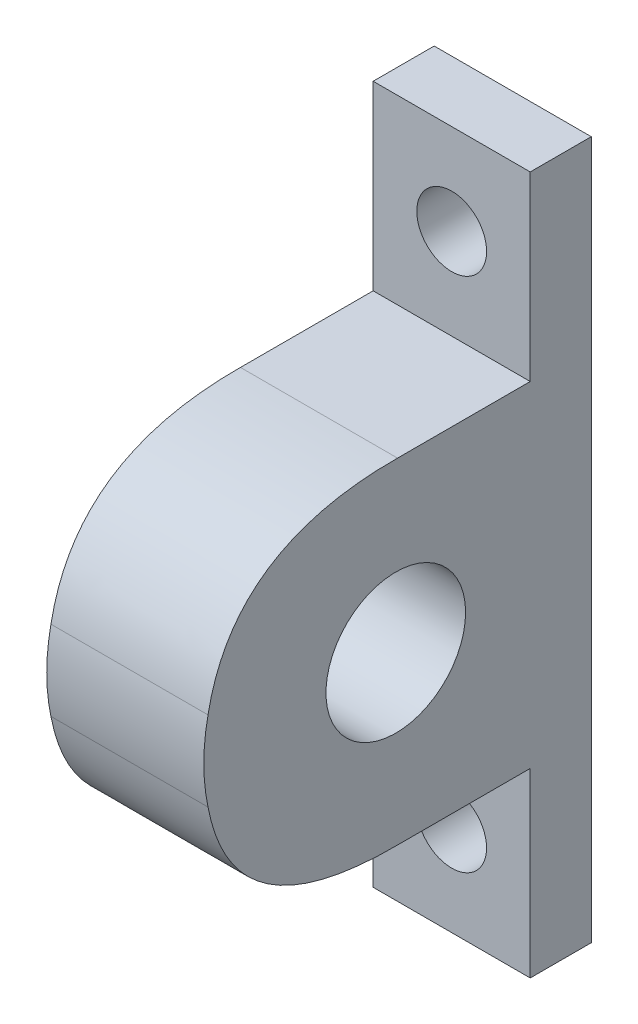
SolidWorks part; units mm, degrees
ref_plane "Front Plane" through (0, 0, 0) normal (1, 0, 0) x (0, 1, 0)
ref_plane "Top Plane" through (0, 0, 0) normal (0, 0, 1) x (0, 1, 0)
ref_plane "Right Plane" through (0, 0, 0) normal (0, 1, 0) x (-1, 0, 0)
sketch "Sketch1" plane through (0, 0, 0) normal (0, 0, 1) x (0, 1, 0)
  line L0 (-50, 0) -> (50, 0)
  line L1 (-50, 0) -> (-50, -22.5)
  line L2 (-50, -22.5) -> (50, -22.5)
  line L3 (50, -22.5) -> (50, 0)
  point P4 (0, 0)
  dimension "D1" = 100
  dimension "D2" = 22.5
extrude "Boss-Extrude1" add sketch "Sketch1" along normal blind 55.5
sketch "Sketch2" plane through (22.5, 0, 0) normal (1, 0, 0) x (0, 1, 0)
  line L0 (0, 0) -> (0, 0.5)
  line L1 (-24, 0) -> (-24, 55.5)
  line L2 (-50, 0) -> (50, 0) construction
  line L4 (-50, 55.5) -> (-50, 0) construction
  line L5 (50, 55.5) -> (50, 0) construction
  line L6 (19.6311, 8.742) -> (50, 8.742)
  line L8 (50, 55.5) -> (50, 14.5743)
  line L10 (-50, 55.5) -> (50, 55.5) construction
  line L12 (24, 0) -> (24, 55.5)
  line L13 (0, 0.5) -> (0, 55.5)
  line L14 (-24, 8.742) -> (-19.6311, 8.742)
  line L15 (-24, 8.742) -> (-50, 8.742)
  circle A4 centre (0, 28) radius 27.5
  circle A5 centre (0, 28) radius 10
  spline S0 degree 2 poles (0, 55.5) (-24.2004, 54.7772) (-24, 27.75) knots 0 0 0 1 1 1
  spline S1 degree 2 poles (0, 55.5) (24.2004, 54.7772) (24, 27.75) knots 0 0 0 1 1 1
  line M7 (50, 0) -> (50, 55.5)
  line M8 (50, 55.5) -> (-50, 55.5)
  line M9 (-50, 55.5) -> (-50, 0)
  dimension "D2" = 20
  dimension "D1" = 0.5
extrude "Cut-Extrude1" cut sketch "Sketch2" against normal through all contours A4 L1 L15 M8 M9 | S0 L1 A4 | S0 A4 L1 | S0 A4 L1 M8 | L13 A5 | L13 A5 | A4 S1 L12 M8 | A4 L12 L6 M7 M8 | L12 S1 A4 | A4 S1 L12
sketch "Sketch3" plane through (0, 0, 8.742) normal (0, 0, 1) x (1, 0, 0)
  line L0 (22.5, 50) -> (0, 24)
  circle A0 centre (11.25, 37) radius 5
  dimension "D1" = 10
extrude "Cut-Extrude2" cut sketch "Sketch3" against normal through all contours L0 A0 | L0 A0 region at (12.8546, 35.6114, 8.742) region at (9.6454, 38.3886, 8.742)
sketch "Sketch5" plane through (0, 0, 8.742) normal (0, 0, 1) x (1, 0, 0)
  line L0 (0, -24) -> (22.5, -50)
  circle A0 centre (11.25, -37) radius 4.9984
extrude "Cut-Extrude3" cut sketch "Sketch5" against normal through all contours L0 A0 | L0 A0 region at (12.8541, -35.6118, 8.742) region at (9.6459, -38.3882, 8.742)
sketch "Sketch6" plane through (0, 0, 0) normal (-1, 0, 0) x (0, -1, 0)
  circle A0 centre (0, 28) radius 12
  circle M1 centre (0, 28) radius 10
  dimension "D1" = 24
extrude "Boss-Extrude2" add sketch "Sketch6" along normal blind 5 contours A0 M1 region at (0, 11.6606, 28)
